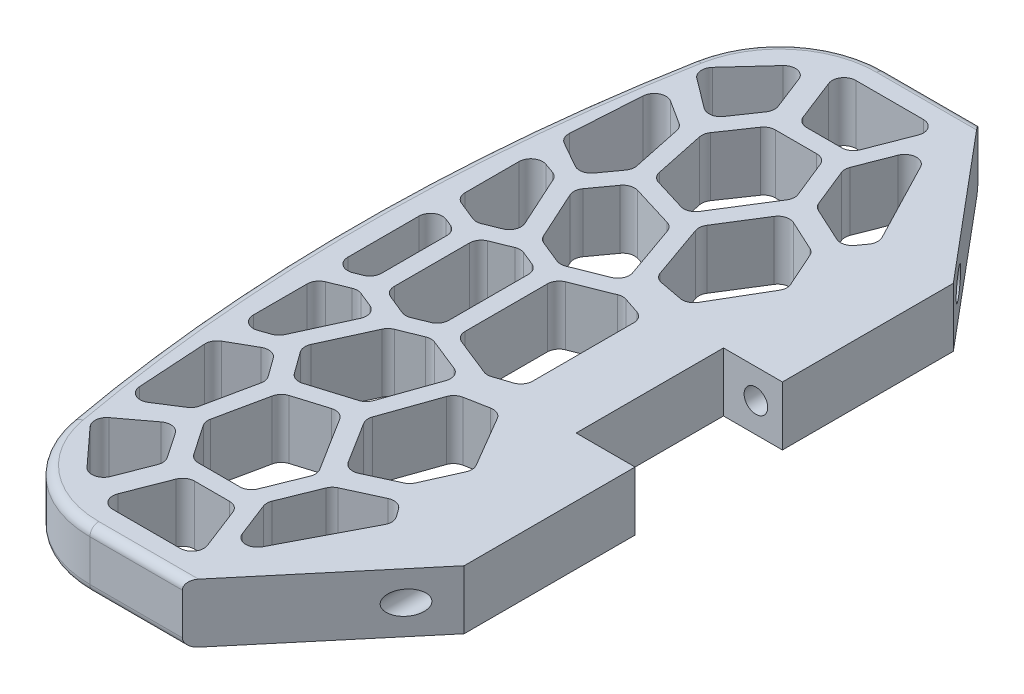
SolidWorks part; units mm, degrees
material "6061 Alloy"
ref_plane "Спереди" through (0, 0, 0) normal (0, 0, 1) x (1, 0, 0)
ref_plane "Сверху" through (0, 0, 0) normal (0, 1, 0) x (1, 0, 0)
ref_plane "Справа" through (0, 0, 0) normal (1, 0, 0) x (0, 0, -1)
other "Configuration Table"
sketch "Sketch1" plane through (0, 0, 0) normal (0, 1, 0) x (1, 0, 0)
  line L0 (0, 83) -> (-43.6332, 135)
  line L1 (-120, 135) -> (0, 135) construction
  line L3 (-120, -135) -> (0, -135) construction
  line L4 (0, 135) -> (0, -135) construction
  line L5 (-43.6332, 135) -> (-75, 135)
  line L6 (0, -83) -> (-43.6332, -135)
  line L7 (0, 83) -> (0, 25)
  line L8 (0, 25) -> (-20, 25)
  line L9 (-20, 25) -> (-20, -25)
  line L10 (-20, -25) -> (0, -25)
  line L11 (-134.8601, 0) -> (61.7365, 0) construction
  line L12 (-89.1294, -199.9223) -> (-89.1294, 67.4111) construction
  line L13 (-120, 135) -> (-120, -135) construction
  line L14 (-43.6332, -135) -> (-75, -135)
  line L15 (0, -83) -> (0, -25)
  line L16 (-51.5835, -99.5519) -> (-47.044, -111.2449)
  line L17 (-39.7668, -111.6438) -> (-25.558, -84.3396)
  line L18 (-32.7123, -76.168) -> (-44.2897, -81.4925)
  line L19 (-46.3278, -83.6299) -> (-51.5641, -96.6076)
  line L20 (-76.1692, -126.0674) -> (-53.2432, -126.0674)
  line L21 (-49.5143, -120.6197) -> (-55.0229, -106.4306)
  line L22 (-58.7518, -103.8782) -> (-70.6335, -103.8782)
  line L23 (-74.3599, -106.4244) -> (-79.8956, -120.6136)
  line L24 (-104.3144, -105.6227) -> (-92.9037, -118.071)
  line L25 (-86.2286, -116.822) -> (-81.7314, -105.2948)
  line L26 (-82.1529, -101.5877) -> (-87.9561, -93.0762)
  line L27 (-93.6634, -92.1313) -> (-103.7682, -99.7216)
  line L28 (-110.4098, -12.0561) -> (-110.4098, 12.0561)
  line L29 (-104.9035, 15.7616) -> (-102.4473, 14.7632)
  line L30 (-99.9536, 11.0577) -> (-99.9536, -11.0577)
  line L31 (-102.4473, -14.7632) -> (-104.9035, -15.7616)
  line L32 (-91.46, 16.4616) -> (-84.9311, 19.1157)
  line L33 (-81.9184, 19.1157) -> (-77.2039, 17.1992)
  line L34 (-74.7102, 13.4937) -> (-74.7102, -13.4937)
  line L35 (-77.2039, -17.1992) -> (-81.9184, -19.1157)
  line L36 (-84.9311, -19.1157) -> (-91.46, -16.4616)
  line L37 (-93.9536, -12.7561) -> (-93.9536, 12.7561)
  line L38 (-68.7102, -13.9388) -> (-68.7102, 13.9388)
  line L39 (-66.193, 17.6539) -> (-53.5974, 22.6809)
  line L40 (-50.851, 22.761) -> (-45.3523, 20.93)
  line L41 (-42.6161, 17.1349) -> (-42.6161, -17.1349)
  line L42 (-45.3523, -20.93) -> (-50.851, -22.761)
  line L43 (-53.5974, -22.6809) -> (-66.193, -17.6539)
  line L44 (-109.4672, -45.085) -> (-109.4672, -26.7855)
  line L45 (-106.9735, -23.0799) -> (-100.549, -20.4683)
  line L46 (-97.5364, -20.4683) -> (-92.4294, -22.5443)
  line L47 (-90.2975, -27.912) -> (-98.3379, -45.5117)
  line L48 (-100.6417, -47.6203) -> (-104.1327, -48.8558)
  line L49 (-91.0282, -43.9506) -> (-83.4663, -27.3984)
  line L50 (-81.3343, -25.355) -> (-73.7854, -22.2863)
  line L51 (-70.7963, -22.2768) -> (-59.788, -26.6704)
  line L52 (-57.4974, -31.7129) -> (-63.8788, -49.851)
  line L53 (-66.4825, -52.3487) -> (-80.926, -56.7647)
  line L54 (-85.3376, -55.2823) -> (-90.6321, -47.9556)
  line L55 (-109.1859, -61.8731) -> (-107.7167, -85.4548)
  line L56 (-101.576, -88.5801) -> (-93.5679, -83.481)
  line L57 (-91.8022, -80.9315) -> (-88.1953, -63.8092)
  line L58 (-88.8673, -60.6419) -> (-93.373, -54.4066)
  line L59 (-98.5914, -53.2717) -> (-107.1699, -58.1467)
  line L60 (-59.2517, -54.778) -> (-52.7411, -36.2726)
  line L61 (-49.7099, -33.6696) -> (-41.8514, -32.1859)
  line L62 (-37.6591, -34.0926) -> (-27.4855, -51.4361)
  line L63 (-27.2853, -55.0953) -> (-32.5729, -66.8979)
  line L64 (-34.5425, -68.8922) -> (-45.0179, -73.7431)
  line L65 (-50.088, -72.2377) -> (-58.8677, -58.2299)
  line L66 (-86.0989, -82.9648) -> (-82.4552, -65.668)
  line L67 (-79.7106, -62.6673) -> (-68.759, -59.3189)
  line L68 (-64.2002, -61.0198) -> (-52.797, -79.2134)
  line L69 (-52.4768, -82.8344) -> (-57.5367, -95.3749)
  line L70 (-61.2462, -97.8782) -> (-75.3061, -97.8782)
  line L71 (-78.6111, -96.1315) -> (-85.4897, -86.0427)
  line L72 (-27.7933, -77.4671) -> (-25.8585, -80.1581)
  line L73 (-27.7933, 77.4671) -> (-25.8585, 80.1581)
  line L74 (-78.6111, 96.1315) -> (-85.4897, 86.0427)
  line L75 (-61.2462, 97.8782) -> (-75.3061, 97.8782)
  line L76 (-52.4768, 82.8344) -> (-57.5367, 95.3749)
  line L77 (-64.2002, 61.0198) -> (-52.797, 79.2134)
  line L78 (-79.7106, 62.6673) -> (-68.759, 59.3189)
  line L79 (-86.0989, 82.9648) -> (-82.4552, 65.668)
  line L80 (-50.088, 72.2377) -> (-58.8677, 58.2299)
  line L81 (-34.5425, 68.8922) -> (-45.0179, 73.7431)
  line L82 (-27.2853, 55.0953) -> (-32.5729, 66.8979)
  line L83 (-37.6591, 34.0926) -> (-27.4855, 51.4361)
  line L84 (-49.7099, 33.6696) -> (-41.8514, 32.1859)
  line L85 (-59.2517, 54.778) -> (-52.7411, 36.2726)
  line L86 (-98.5914, 53.2717) -> (-107.1699, 58.1467)
  line L87 (-88.8673, 60.6419) -> (-93.373, 54.4066)
  line L88 (-91.8022, 80.9315) -> (-88.1953, 63.8092)
  line L89 (-101.576, 88.5801) -> (-93.5679, 83.481)
  line L90 (-109.1859, 61.8731) -> (-107.7167, 85.4548)
  line L91 (-85.3376, 55.2823) -> (-90.6321, 47.9556)
  line L92 (-66.4825, 52.3487) -> (-80.926, 56.7647)
  line L93 (-57.4974, 31.7129) -> (-63.8788, 49.851)
  line L94 (-70.7963, 22.2768) -> (-59.788, 26.6704)
  line L95 (-81.3343, 25.355) -> (-73.7854, 22.2863)
  line L96 (-91.0282, 43.9506) -> (-83.4663, 27.3984)
  line L97 (-100.6417, 47.6203) -> (-104.1327, 48.8558)
  line L98 (-90.2975, 27.912) -> (-98.3379, 45.5117)
  line L99 (-97.5364, 20.4683) -> (-92.4294, 22.5443)
  line L100 (-106.9735, 23.0799) -> (-100.549, 20.4683)
  line L101 (-109.4672, 45.085) -> (-109.4672, 26.7855)
  line L102 (-93.6634, 92.1313) -> (-103.7682, 99.7216)
  line L103 (-82.1529, 101.5877) -> (-87.9561, 93.0762)
  line L104 (-86.2286, 116.822) -> (-81.7314, 105.2948)
  line L105 (-104.3144, 105.6227) -> (-92.9037, 118.071)
  line L106 (-74.3599, 106.4244) -> (-79.8956, 120.6136)
  line L107 (-58.7518, 103.8782) -> (-70.6335, 103.8782)
  line L108 (-49.5143, 120.6197) -> (-55.0229, 106.4306)
  line L109 (-76.1692, 126.0674) -> (-53.2432, 126.0674)
  line L110 (-46.3278, 83.6299) -> (-51.5641, 96.6076)
  line L111 (-32.7123, 76.168) -> (-44.2897, 81.4925)
  line L112 (-39.7668, 111.6438) -> (-25.558, 84.3396)
  line L113 (-51.5835, 99.5519) -> (-47.044, 111.2449)
  line L114 (-43.6332, 135) -> (-75, 135)
  arc A0 (-75, 135) -> (-110.4098, 105.4918) centre (-75, 99) ccw
  arc A1 (-110.4098, 105.4918) -> (-110.4098, -105.4918) centre (465, 0) ccw
  arc A2 (-75, -135) -> (-110.4098, -105.4918) centre (-75, -99) cw
  arc A3 (-59.2517, -54.778) -> (-58.8677, -58.2299) centre (-55.4784, -56.1056) ccw
  arc A4 (-52.7411, -36.2726) -> (-49.7099, -33.6696) centre (-48.9678, -37.6002) cw
  arc A5 (-41.8514, -32.1859) -> (-37.6591, -34.0926) centre (-41.1093, -36.1164) cw
  arc A6 (-27.4855, -51.4361) -> (-27.2853, -55.0953) centre (-30.9357, -53.4599) cw
  arc A7 (-32.5729, -66.8979) -> (-34.5425, -68.8922) centre (-36.2233, -65.2625) cw
  arc A8 (-45.0179, -73.7431) -> (-50.088, -72.2377) centre (-46.6987, -70.1134) cw
  arc A9 (-25.8585, -80.1581) -> (-25.558, -84.3396) centre (-29.1062, -82.4931) cw
  arc A10 (-27.7933, -77.4671) -> (-32.7123, -76.168) centre (-31.041, -79.8021) ccw
  arc A11 (-44.2897, -81.4925) -> (-46.3278, -83.6299) centre (-42.6184, -85.1266) ccw
  arc A12 (-51.5835, -99.5519) -> (-51.5641, -96.6076) centre (-47.8547, -98.1043) cw
  arc A13 (-47.044, -111.2449) -> (-39.7668, -111.6438) centre (-43.3151, -109.7973) ccw
  arc A14 (-53.2432, -126.0674) -> (-49.5143, -120.6197) centre (-53.2432, -122.0674) ccw
  arc A15 (-76.1692, -126.0674) -> (-79.8956, -120.6136) centre (-76.1692, -122.0674) cw
  arc A16 (-55.0229, -106.4306) -> (-58.7518, -103.8782) centre (-58.7518, -107.8782) ccw
  arc A17 (-70.6335, -103.8782) -> (-74.3599, -106.4244) centre (-70.6335, -107.8782) ccw
  arc A18 (-52.797, -79.2134) -> (-52.4768, -82.8344) centre (-56.1863, -81.3377) cw
  arc A19 (-57.5367, -95.3749) -> (-61.2462, -97.8782) centre (-61.2462, -93.8782) cw
  arc A20 (-75.3061, -97.8782) -> (-78.6111, -96.1315) centre (-75.3061, -93.8782) cw
  arc A21 (-86.0989, -82.9648) -> (-85.4897, -86.0427) centre (-82.1848, -83.7894) ccw
  arc A22 (-68.759, -59.3189) -> (-64.2002, -61.0198) centre (-67.5895, -63.1441) cw
  arc A23 (-82.4552, -65.668) -> (-79.7106, -62.6673) centre (-78.5411, -66.4925) cw
  arc A24 (-93.5679, -83.481) -> (-91.8022, -80.9315) centre (-95.7163, -80.1069) ccw
  arc A25 (-88.1953, -63.8092) -> (-88.8673, -60.6419) centre (-92.1094, -62.9847) ccw
  arc A26 (-93.373, -54.4066) -> (-98.5914, -53.2717) centre (-96.6151, -56.7494) ccw
  arc A27 (-81.7314, -105.2948) -> (-82.1529, -101.5877) centre (-85.4578, -103.841) ccw
  arc A28 (-87.9561, -93.0762) -> (-93.6634, -92.1313) centre (-91.261, -95.3295) ccw
  arc A29 (-92.9037, -118.071) -> (-86.2286, -116.822) centre (-89.955, -115.3682) ccw
  arc A30 (-104.3144, -105.6227) -> (-103.7682, -99.7216) centre (-101.3658, -102.9198) cw
  arc A31 (-109.1859, -61.8731) -> (-107.1699, -58.1467) centre (-105.1936, -61.6244) cw
  arc A32 (-107.7167, -85.4548) -> (-101.576, -88.5801) centre (-103.7245, -85.2061) ccw
  arc A33 (-80.926, -56.7647) -> (-85.3376, -55.2823) centre (-82.0955, -52.9395) cw
  arc A34 (-63.8788, -49.851) -> (-66.4825, -52.3487) centre (-67.6521, -48.5235) cw
  arc A35 (-59.788, -26.6704) -> (-57.4974, -31.7129) centre (-61.2707, -30.3854) cw
  arc A36 (-73.7854, -22.2863) -> (-70.7963, -22.2768) centre (-72.279, -25.9919) cw
  arc A37 (-83.4663, -27.3984) -> (-81.3343, -25.355) centre (-79.828, -29.0606) cw
  arc A38 (-91.0282, -43.9506) -> (-90.6321, -47.9556) centre (-87.3899, -45.6128) ccw
  arc A39 (-98.3379, -45.5117) -> (-100.6417, -47.6203) centre (-101.9762, -43.8495) cw
  arc A40 (-109.4672, -45.085) -> (-104.1327, -48.8558) centre (-105.4672, -45.085) ccw
  arc A41 (-92.4294, -22.5443) -> (-90.2975, -27.912) centre (-93.9358, -26.2499) cw
  arc A42 (-100.549, -20.4683) -> (-97.5364, -20.4683) centre (-99.0427, -24.1739) cw
  arc A43 (-109.4672, -26.7855) -> (-106.9735, -23.0799) centre (-105.4672, -26.7855) cw
  arc A44 (-74.7102, -13.4937) -> (-77.2039, -17.1992) centre (-78.7102, -13.4937) cw
  arc A45 (-91.46, -16.4616) -> (-93.9536, -12.7561) centre (-89.9536, -12.7561) cw
  arc A46 (-81.9184, -19.1157) -> (-84.9311, -19.1157) centre (-83.4248, -15.4101) cw
  arc A47 (-42.6161, -17.1349) -> (-45.3523, -20.93) centre (-46.6161, -17.1349) cw
  arc A48 (-50.851, -22.761) -> (-53.5974, -22.6809) centre (-52.1147, -18.9659) cw
  arc A49 (-68.7102, -13.9388) -> (-66.193, -17.6539) centre (-64.7102, -13.9388) ccw
  arc A50 (-45.3523, 20.93) -> (-42.6161, 17.1349) centre (-46.6161, 17.1349) cw
  arc A51 (-53.5974, 22.6809) -> (-50.851, 22.761) centre (-52.1147, 18.9659) cw
  arc A52 (-68.7102, 13.9388) -> (-66.193, 17.6539) centre (-64.7102, 13.9388) cw
  arc A53 (-77.2039, 17.1992) -> (-74.7102, 13.4937) centre (-78.7102, 13.4937) cw
  arc A54 (-84.9311, 19.1157) -> (-81.9184, 19.1157) centre (-83.4248, 15.4101) cw
  arc A55 (-91.46, 16.4616) -> (-93.9536, 12.7561) centre (-89.9536, 12.7561) ccw
  arc A56 (-99.9536, -11.0577) -> (-102.4473, -14.7632) centre (-103.9536, -11.0577) cw
  arc A57 (-110.4098, -12.0561) -> (-104.9035, -15.7616) centre (-106.4098, -12.0561) ccw
  arc A58 (-102.4473, 14.7632) -> (-99.9536, 11.0577) centre (-103.9536, 11.0577) cw
  arc A59 (-110.4098, 12.0561) -> (-104.9035, 15.7616) centre (-106.4098, 12.0561) cw
  arc A60 (-109.4672, 26.7855) -> (-106.9735, 23.0799) centre (-105.4672, 26.7855) ccw
  arc A61 (-92.4294, 22.5443) -> (-90.2975, 27.912) centre (-93.9358, 26.2499) ccw
  arc A62 (-109.4672, 45.085) -> (-104.1327, 48.8558) centre (-105.4672, 45.085) cw
  arc A63 (-98.3379, 45.5117) -> (-100.6417, 47.6203) centre (-101.9762, 43.8495) ccw
  arc A64 (-91.0282, 43.9506) -> (-90.6321, 47.9556) centre (-87.3899, 45.6128) cw
  arc A65 (-83.4663, 27.3984) -> (-81.3343, 25.355) centre (-79.828, 29.0606) ccw
  arc A66 (-73.7854, 22.2863) -> (-70.7963, 22.2768) centre (-72.279, 25.9919) ccw
  arc A67 (-59.788, 26.6704) -> (-57.4974, 31.7129) centre (-61.2707, 30.3854) ccw
  arc A68 (-63.8788, 49.851) -> (-66.4825, 52.3487) centre (-67.6521, 48.5235) ccw
  arc A69 (-80.926, 56.7647) -> (-85.3376, 55.2823) centre (-82.0955, 52.9395) ccw
  arc A70 (-107.7167, 85.4548) -> (-101.576, 88.5801) centre (-103.7245, 85.2061) cw
  arc A71 (-109.1859, 61.8731) -> (-107.1699, 58.1467) centre (-105.1936, 61.6244) ccw
  arc A72 (-104.3144, 105.6227) -> (-103.7682, 99.7216) centre (-101.3658, 102.9198) ccw
  arc A73 (-92.9037, 118.071) -> (-86.2286, 116.822) centre (-89.955, 115.3682) cw
  arc A74 (-87.9561, 93.0762) -> (-93.6634, 92.1313) centre (-91.261, 95.3295) cw
  arc A75 (-81.7314, 105.2948) -> (-82.1529, 101.5877) centre (-85.4578, 103.841) cw
  arc A76 (-93.373, 54.4066) -> (-98.5914, 53.2717) centre (-96.6151, 56.7494) cw
  arc A77 (-88.1953, 63.8092) -> (-88.8673, 60.6419) centre (-92.1094, 62.9847) cw
  arc A78 (-93.5679, 83.481) -> (-91.8022, 80.9315) centre (-95.7163, 80.1069) cw
  arc A79 (-82.4552, 65.668) -> (-79.7106, 62.6673) centre (-78.5411, 66.4925) ccw
  arc A80 (-68.759, 59.3189) -> (-64.2002, 61.0198) centre (-67.5895, 63.1441) ccw
  arc A81 (-86.0989, 82.9648) -> (-85.4897, 86.0427) centre (-82.1848, 83.7894) cw
  arc A82 (-75.3061, 97.8782) -> (-78.6111, 96.1315) centre (-75.3061, 93.8782) ccw
  arc A83 (-57.5367, 95.3749) -> (-61.2462, 97.8782) centre (-61.2462, 93.8782) ccw
  arc A84 (-52.797, 79.2134) -> (-52.4768, 82.8344) centre (-56.1863, 81.3377) ccw
  arc A85 (-70.6335, 103.8782) -> (-74.3599, 106.4244) centre (-70.6335, 107.8782) cw
  arc A86 (-55.0229, 106.4306) -> (-58.7518, 103.8782) centre (-58.7518, 107.8782) cw
  arc A87 (-76.1692, 126.0674) -> (-79.8956, 120.6136) centre (-76.1692, 122.0674) ccw
  arc A88 (-53.2432, 126.0674) -> (-49.5143, 120.6197) centre (-53.2432, 122.0674) cw
  arc A89 (-47.044, 111.2449) -> (-39.7668, 111.6438) centre (-43.3151, 109.7973) cw
  arc A90 (-51.5835, 99.5519) -> (-51.5641, 96.6076) centre (-47.8547, 98.1043) ccw
  arc A91 (-44.2897, 81.4925) -> (-46.3278, 83.6299) centre (-42.6184, 85.1266) cw
  arc A92 (-27.7933, 77.4671) -> (-32.7123, 76.168) centre (-31.041, 79.8021) cw
  arc A93 (-25.8585, 80.1581) -> (-25.558, 84.3396) centre (-29.1062, 82.4931) ccw
  arc A94 (-45.0179, 73.7431) -> (-50.088, 72.2377) centre (-46.6987, 70.1134) ccw
  arc A95 (-32.5729, 66.8979) -> (-34.5425, 68.8922) centre (-36.2233, 65.2625) ccw
  arc A96 (-27.4855, 51.4361) -> (-27.2853, 55.0953) centre (-30.9357, 53.4599) ccw
  arc A97 (-41.8514, 32.1859) -> (-37.6591, 34.0926) centre (-41.1093, 36.1164) ccw
  arc A98 (-52.7411, 36.2726) -> (-49.7099, 33.6696) centre (-48.9678, 37.6002) ccw
  arc A99 (-59.2517, 54.778) -> (-58.8677, 58.2299) centre (-55.4784, 56.1056) cw
  arc A100 (-100.549, 20.4683) -> (-97.5364, 20.4683) centre (-99.0427, 24.1739) ccw
  point P155 (-99.0427, -47.0544)
  point P158 (-109.4672, -50.7438)
  point P193 (-110.4098, -18)
  point P198 (-110.4098, 18)
  point P321 (-99.0427, 47.0544)
  dimension "D7" = 36
  dimension "D25" = 4
  dimension "D1" = 120
  dimension "D2" = 270
  dimension "D3" = 40
  dimension "D4" = 20
  dimension "D5" = 50
  dimension "D6" = 58
  dimension "D8" = 75
  dimension "D9" = 6
  dimension "D10" = 6
  dimension "D11" = 6
  dimension "D12" = 6
  dimension "D13" = 6
  dimension "D14" = 6
  dimension "D15" = 6
  dimension "D16" = 6
  dimension "D17" = 6
  dimension "D18" = 6
  dimension "D19" = 6
  dimension "D20" = 36
  dimension "D21" = 6
  dimension "D22" = 6
  dimension "D23" = 6
  dimension "D24" = 6
extrude "Boss-Extrude1" add sketch "Sketch1" along normal mid plane 20 contours A2 L14 L6 L15 L10 L9 L8 L7 L0 L5 A0 A1 A100 L100 A60 L101 A62 L97 A63 L98 A61 L99 A93 L73 A92 L111 A91 L110 A90 L113 A89 L112 A84 L77 A80 L78 A79 L79 A81 L74 A82 L75 A83 L76 A69 L92 A68 region at (-2.9547, 0, -54)
fillet "Fillet1" radius 3 10 edges at (-59.3166, 10, -135) (-98.0466, 10, -126.656) (-59.3166, 10, 135) (-98.0466, 10, 126.656) (-59.3166, -10, -135) (-98.0466, -10, -126.656) (-59.3166, -10, 135) (-98.0466, -10, 126.656) (-120, 10, 0) (-120, -10, 0)
sketch "Sketch2" plane through (0, 0, 0) normal (0, 0, 1) x (1, 0, 0)
  circle A0 centre (-9, 0) radius 4
  dimension "D1" = 8
  dimension "D2" = 9
extrude "Cut-Extrude1" cut sketch "Sketch2" against normal through all both and the other way through all
equation "\"D10@Sketch1\"=\"D9@Sketch1\""
equation "\"D11@Sketch1\"=\"D9@Sketch1\""
equation "\"D12@Sketch1\"=\"D9@Sketch1\""
equation "\"D13@Sketch1\"=\"D9@Sketch1\""
equation "\"D14@Sketch1\"=\"D9@Sketch1\""
equation "\"D15@Sketch1\"=\"D9@Sketch1\""
equation "\"D16@Sketch1\"=\"D9@Sketch1\""
equation "\"D17@Sketch1\"=\"D9@Sketch1\""
equation "\"D18@Sketch1\"=\"D9@Sketch1\""
equation "\"D19@Sketch1\"=\"D9@Sketch1\""
equation "\"D21@Sketch1\"=\"D9@Sketch1\""
equation "\"D22@Sketch1\"=\"D9@Sketch1\""
equation "\"D23@Sketch1\"=\"D9@Sketch1\""
equation "\"D24@Sketch1\"=\"D9@Sketch1\""
